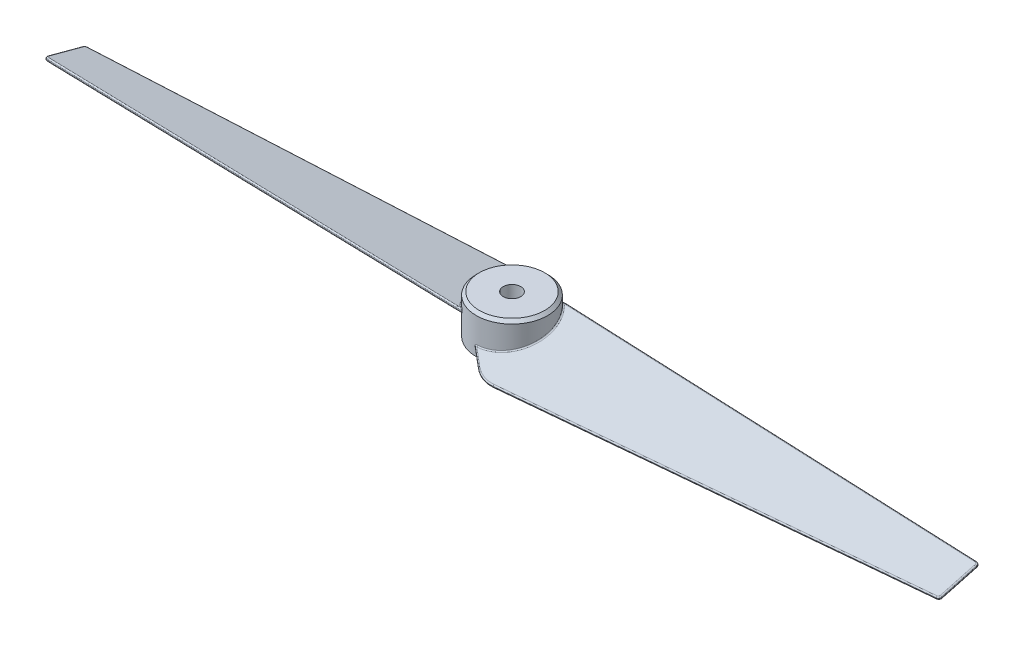
SolidWorks part; units mm, degrees
material "PTFE (allgemein)"
ref_plane "Ebene vorne" through (0, 0, 0) normal (0, 0, 1) x (1, 0, 0)
ref_plane "Ebene oben" through (0, 0, 0) normal (0, 1, 0) x (1, 0, 0)
ref_plane "Ebene rechts" through (0, 0, 0) normal (1, 0, 0) x (0, 0, -1)
sketch "Skizze1" plane through (0, 0, 0) normal (0, 1, 0) x (1, 0, 0)
  circle A0 centre (0, 0) radius 1.475
  circle A1 centre (0, 0) radius 6
  dimension "D1" = 2.95
  dimension "D2" = 12
extrude "Aufnahme" add sketch "Skizze1" along normal blind 7
chamfer "Aufnahmefase" distance 0.5 angle 45 2 edges at (0, 0, 6) (0, 7, 6)
ref_plane "Hilfsebene1" through (0, 3.5, 0) normal (0, 1, 0) x (1, 0, 0)
ref_axis "Hilfsachse1" through (88.99, 3.5, 0) along (-1, 0, 0)
ref_plane "Propellerebene" through (0, 3.2655, 0.875) normal (0, 0.9659, 0.2588) x (-1, 0, 0)
sketch "Skizze2" plane through (0, 3.2655, 0.875) normal (0, 0.9659, 0.2588) x (-1, 0, 0)
  line L0 (6, -1.8117) -> (-1.475, -1.8117) construction
  line L1 (2.2625, -3.7903) -> (2.2625, 3.556)
  line L2 (2.2625, 3.556) -> (-4.2361, 9.009)
  line L3 (-4.2361, 9.009) -> (-76.2, 3.545)
  line L4 (-76.2, 3.545) -> (-76.2, -3.455)
  line L5 (-76.2, -3.455) -> (-3.7636, -5.9836)
  line L6 (-3.7636, -5.9836) -> (2.2625, -3.7903)
  line L7 (0, 8.2026) -> (0, -13.8166) construction
  ellipse E0 centre (0, -1.8117) end of major axis (-1.475, -1.8117) minor radius 1.4247 construction
  ellipse E1 centre (0, -1.8117) end of major axis (6, -1.8117) minor radius 5.7956 construction
  ellipse E2 centre (0, -1.8117) end of major axis (-1.475, -1.8117) minor radius 1.4247 construction
  ellipse E3 centre (0, -1.8117) end of major axis (6, -1.8117) minor radius 5.7956 construction
  point P30 (2.2625, -1.8117)
  dimension "D1" = 152.4
  dimension "D2" = 15
  dimension "D3" = 7
  dimension "D4" = 40
  dimension "D5" = 20
extrude "Propeller1" add sketch "Skizze2" along normal mid plane 0.5
fillet "Propellerverrundung1" radius 5 2 edges at (4.2361, 0.9338, 9.577) (3.7636, 4.8142, -4.9047)
fillet "Propellerverrundung2" radius 0.5 2 edges at (76.2, 4.1598, -2.4623) (76.2, 2.348, 4.2992)
fillet "Propellerverrundung3" radius 0.2 20 edges at (1.2056, 1.8335, 7.1854) (4.3583, 1.2737, 9.2746) (41.0028, 1.8978, 6.9453) (76.0667, 2.6215, 4.2445) (76.2, 3.4929, 0.9925) (76.0597, 4.3662, -2.2667) (40.0727, 4.7276, -3.6157) (5.6968, 2.7365, 1.8833) (1.2885, 1.3325, 7.1232) (4.3583, 0.7907, 9.1452) (41.0028, 1.4149, 6.8158) (76.0667, 2.1385, 4.1151) (76.2, 3.0099, 0.8631) (76.0597, 3.8832, -2.3961) (40.1328, 4.2441, -3.7431) (5.6456, 3.2145, 2.0316) (-0.1813, 1.8954, 5.9973) (3.5566, 4.7937, -4.8322)
ref_axis "Drehachse" through (0, 7, 0) along (0, -1, 0)
pattern_circular "Propeller_Muster" count 2 every 180 about axis through (0, 7, 0) along (0, -1, 0) of "Propeller1", "Propellerverrundung1", "Propellerverrundung2", "Propellerverrundung3"
ref_plane "Koerperspiegelebene" [suppressed] through (0, 0, 10) normal (0, 0, 1) x (1, 0, 0)
mirror "Koerper_Spiegeln" [suppressed] about plane through (0, 0, 10) normal (0, 0, 1) of bodies 103
delete or keep bodies "Körper-Löschen/beibehalten 1" [suppressed] type delete bodies bodies 103
move or copy body "Körper-Verschieben/Kopieren1" [suppressed] bodies to move or copy 105 copy no translate (0, 0, -20)
